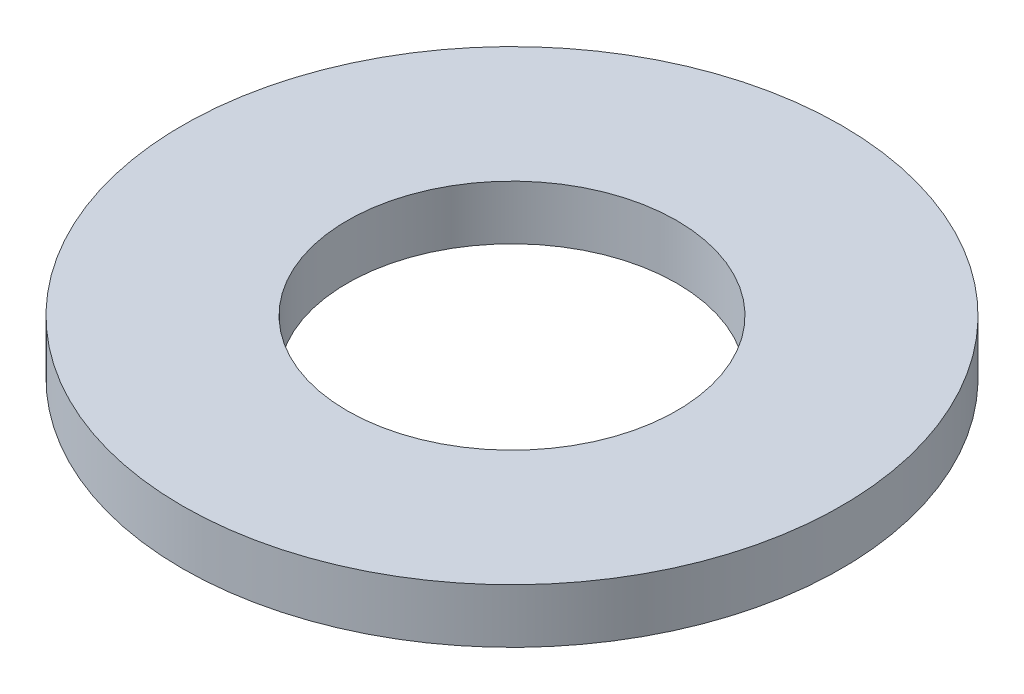
SolidWorks part; units mm, degrees
ref_plane "Front Plane" through (0, 0, 0) normal (0, 0, 1) x (1, 0, 0)
ref_plane "Top Plane" through (0, 0, 0) normal (0, 1, 0) x (1, 0, 0)
ref_plane "Right Plane" through (0, 0, 0) normal (1, 0, 0) x (0, 0, -1)
sketch "Sketch1" plane through (0, 0, 0) normal (0, 1, 0) x (1, 0, 0)
  circle A0 centre (0, 0) radius 85
  dimension "FLANGE_OD" = 170
extrude "Boss-Extrude1" add sketch "Sketch1" along normal blind 14
sketch "Sketch2" plane through (0, 0, 0) normal (0, 1, 0) x (1, 0, 0)
  circle A0 centre (0, 0) radius 42.5
  dimension "BORE_D" = 85
extrude "Cut-Extrude1" cut sketch "Sketch2" along normal through all
sketch "Sketch3" plane through (0, 14, 0) normal (0, 1, 0) x (1, 0, 0)
  circle A0 centre (0, 0) radius 32.5757 construction
  circle A1 centre (-32.5757, 0) radius 3.9753
  dimension "BOLT_D" = 7.9506
  dimension "BOLT_PCD" = 65.1515
extrude "Cut-Extrude2" cut sketch "Sketch3" against normal blind 9.0753 rebuild error yes
pattern_circular "CirPattern1" count 5 over 360 rebuild error yes
